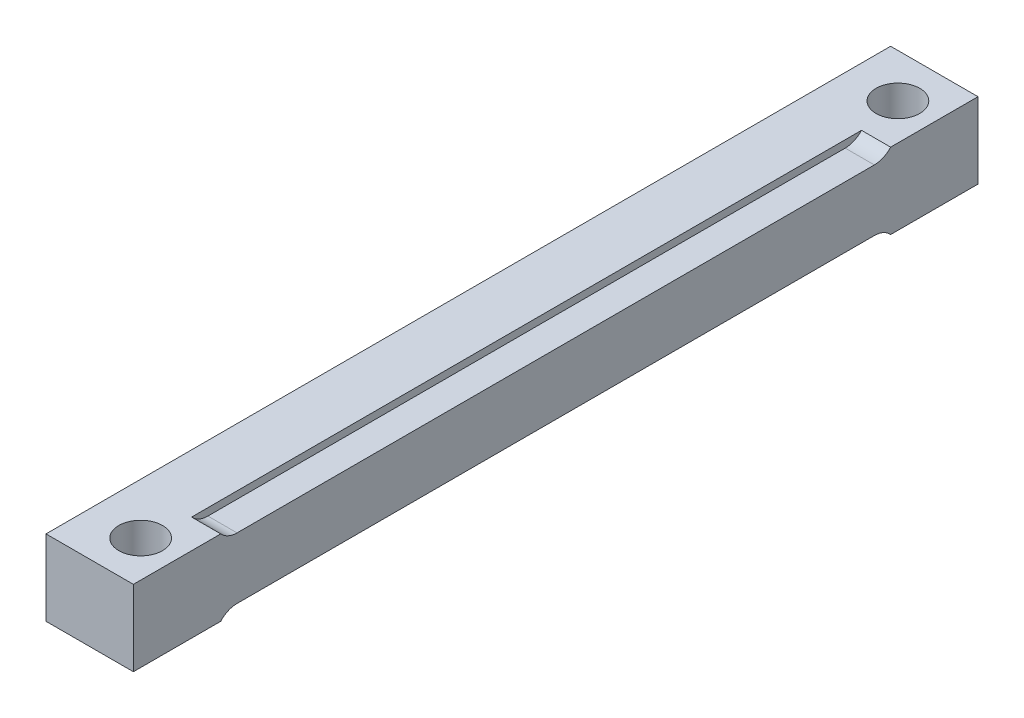
SolidWorks part; units mm, degrees
ref_plane "Front Plane" through (0, 0, 0) normal (0, 0, 1) x (1, 0, 0)
ref_plane "Top Plane" through (0, 0, 0) normal (0, 1, 0) x (1, 0, 0)
ref_plane "Right Plane" through (0, 0, 0) normal (1, 0, 0) x (0, 0, -1)
sketch "Sketch1" plane through (0, 0, 0) normal (0, 1, 0) x (1, 0, 0)
  line L0 (0, 0) -> (6, 0)
  line L1 (6, 0) -> (6, 58)
  line L2 (6, 58) -> (0, 58)
  line L5 (0, 58) -> (0, 0)
  dimension "D1" = 58
  dimension "D2" = 6
extrude "Boss-Extrude1" add sketch "Sketch1" along normal blind 5.2
sketch "Sketch3" plane through (0, 5.2, 0) normal (0, 1, 0) x (1, 0, 0)
  line L0 (0, 0) -> (6, 0) construction
  line L1 (6, 58) -> (0, 58) construction
  line L2 (6, 0) -> (6, 58) construction
  circle A0 centre (3.5, 55) radius 1.5
  circle A1 centre (3.5, 3) radius 1.5
  dimension "D1" = 3
  dimension "D2" = 3
  dimension "D3" = 3
  dimension "D4" = 2.5
extrude "Cut-Extrude2" cut sketch "Sketch3" against normal up to next
sketch "Sketch4" plane through (6, 0, 0) normal (1, 0, 0) x (0, 0, -1)
  line L0 (0, 5.2) -> (58, 5.2) construction
  line L1 (6, 5.2) -> (52, 5.2)
  line L2 (6, 5.2) -> (6, 4.7)
  line L3 (6, 4.7) -> (52, 4.7)
  line L4 (52, 5.2) -> (52, 4.7)
  line L5 (0, 0) -> (58, 0) construction
  line L6 (6, 0) -> (52, 0)
  line L7 (6, 0) -> (6, 0.5)
  line L8 (6, 0.5) -> (52, 0.5)
  line L9 (52, 0) -> (52, 0.5)
  line L10 (0, 5.2) -> (0, 0) construction
  line L11 (58, 5.2) -> (58, 0) construction
  dimension "D1" = 0.5
  dimension "D2" = 0.5
  dimension "D3" = 6
  dimension "D4" = 6
extrude "Cut-Extrude3" cut sketch "Sketch4" against normal blind 2
fillet "Fillet1" radius 1.5 4 edges at (5, 0.5, -52) (5, 0.5, -6) (5, 4.7, -6) (5, 4.7, -52)
